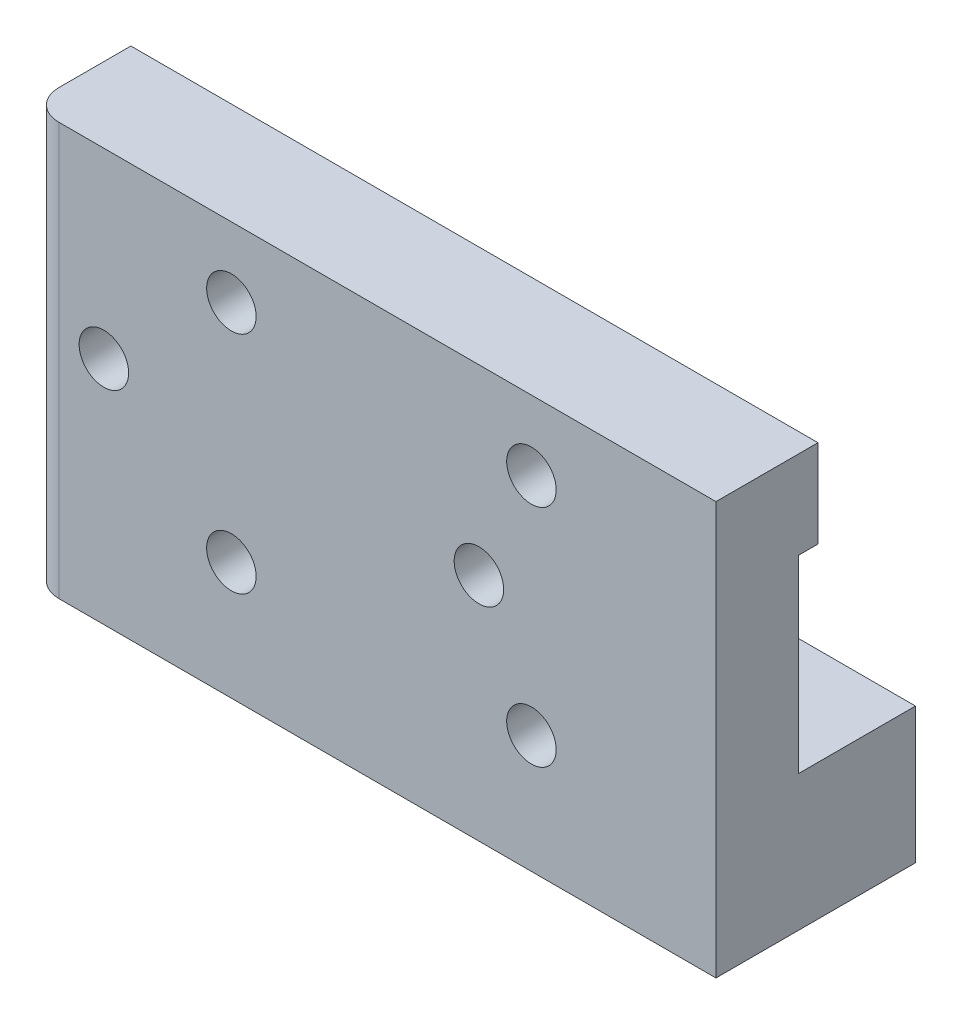
SolidWorks part; units mm, degrees
ref_plane "Front Plane" through (0, 0, 0) normal (0, 0, 1) x (1, 0, 0)
ref_plane "Top Plane" through (0, 0, 0) normal (0, 1, 0) x (1, 0, 0)
ref_plane "Right Plane" through (0, 0, 0) normal (1, 0, 0) x (0, 0, -1)
sketch "Croquis1" plane through (0, 0, 0) normal (0, 0, 1) x (1, 0, 0)
  line L1 (-59.65, -3.2) -> (-13.85, -3.2)
  line L2 (-59.65, -3.2) -> (-59.65, -9.05)
  line L3 (-59.65, -9.05) -> (-13.85, -9.05)
  line L4 (-13.85, -3.2) -> (-13.85, -9.05)
  line L5 (-59.65, -30.7) -> (-13.85, -30.7)
  line L6 (-59.65, -30.7) -> (-59.65, -21.65)
  line L7 (-59.65, -21.65) -> (-13.85, -21.65)
  line L8 (-13.85, -30.7) -> (-13.85, -21.65)
  line L12 (-59.65, -9.05) -> (-13.85, -9.05)
  line L13 (-59.65, -9.05) -> (-59.65, -21.65)
  line L14 (-59.65, -21.65) -> (-13.85, -21.65)
  line L15 (-13.85, -9.05) -> (-13.85, -21.65)
  line L16 (-47.2825, -9.05) -> (-59.65, -9.05) construction
  line L17 (-14.1787, 0) -> (-59.65, 0) construction
  line L18 (-13.65, -11.05) -> (-13.65, -30.7) construction
  line L19 (-59.65, -30.7) -> (-59.65, -9.05) construction
  line L20 (-59.65, -30.7) -> (-13.65, -30.7) construction
  circle A0 centre (-54.65, -15.35) radius 1.65 construction
  circle A1 centre (-54.65, -15.35) radius 1.65
  circle A2 centre (-29.65, -15.35) radius 1.65 construction
  circle A3 centre (-29.65, -15.35) radius 1.65
  circle A4 centre (-46.15, -7.85) radius 1.65 construction
  circle A5 centre (-46.15, -7.85) radius 1.65
  circle A6 centre (-26.15, -7.85) radius 1.65 construction
  circle A7 centre (-26.15, -7.85) radius 1.65
  circle A8 centre (-46.15, -22.85) radius 1.65 construction
  circle A9 centre (-46.15, -22.85) radius 1.65
  circle A10 centre (-26.15, -22.85) radius 1.65 construction
  circle A11 centre (-26.15, -22.85) radius 1.65
  point P12 (0, 0)
  dimension "D1" = 3.2
  dimension "D2" = 0.2
  dimension "D3" = 12.6
extrude "Saliente-Extruir1" add sketch "Croquis1" along normal blind 1.3 from offset 0.1 contours A7 L3 L4 L1 L2 A5 region at (-36.7874, -6.0253, 0)
extrude "Saliente-Extruir3" add sketch "Croquis1<5>" along normal blind 1.3 and the other way blind 6.5 from offset 0.1 separate body contours A11 L7 A9 L6 L5 L8 region at (-36.7736, -26.3011, 0)
sketch "Croquis1<5>" plane through (0, 0, 0) normal (0, 0, 1) x (1, 0, 0) same geometry as "Croquis1"
extrude "Saliente-Extruir2" add sketch "Croquis1<3>" along normal blind 5.5 from surface contours A11 L7 L15 L3 A7 A5 L13 A9 A3 A1 | A7 L3 L4 L1 L2 A5 | A11 L7 A9 L6 L5 L8 region at (-36.7874, -6.0253, 0) region at (-36.5872, -15.35, 0) region at (-36.7736, -26.3011, 0) starting at face at (-36.45, -6.875, 1.4)
sketch "Croquis1<3>" plane through (0, 0, 0) normal (0, 0, 1) x (1, 0, 0) same geometry as "Croquis1"
fillet "Redondeo2" radius 2 1 edges at (-59.65, -16.95, 6.9)
